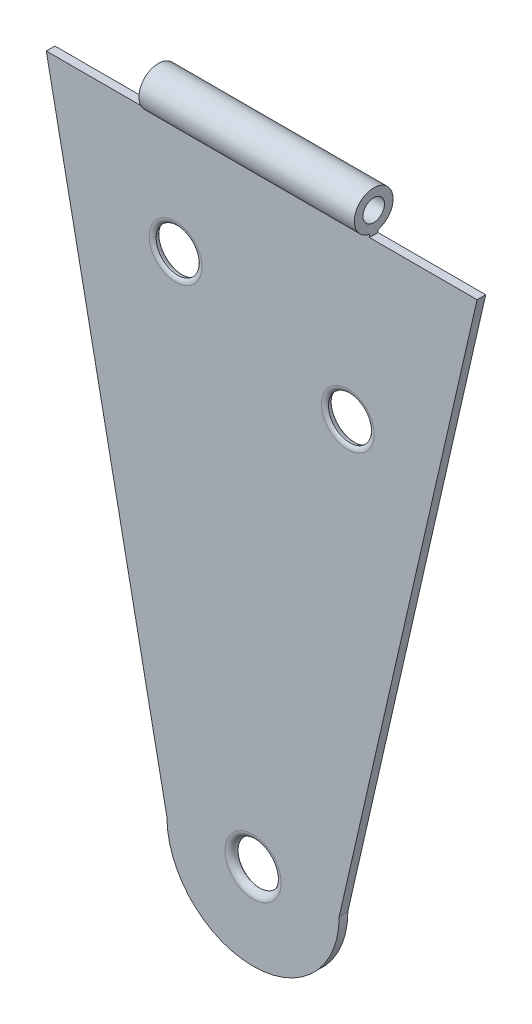
SolidWorks part; units mm, degrees
material "Liga de aço fundido"
ref_plane "Plano frontal" through (0, 0, 0) normal (0, 0, 1) x (1, 0, 0)
ref_plane "Plano superior" through (0, 0, 0) normal (0, 1, 0) x (1, 0, 0)
ref_plane "Plano direito" through (0, 0, 0) normal (1, 0, 0) x (0, 0, -1)
sketch "Esboço1" plane through (0, 0, 0) normal (0, 0, 1) x (1, 0, 0)
  line L0 (-6.1806, 8.1865) -> (-16.1806, 8.1865) construction
  line L2 (-9.8109, 6.3753) -> (-9.8109, 6.1865)
  line L5 (-19.8478, 8.1865) -> (-9.8478, 8.1865)
  line L20 (-9.8109, 6.3753) -> (-9.8109, 6.1865) construction
  line L31 (-19.8478, 8.1865) -> (-17.0478, -5.8135)
  line L33 (-13.0478, -5.8135) -> (-9.8478, 8.1865)
  circle A0 centre (-12.8478, 4.2833) radius 0.5
  circle A5 centre (-16.8478, 5.6526) radius 0.5
  arc A7 (-17.0478, -5.8135) -> (-13.0478, -5.8135) centre (-15.0478, -5.8135) ccw
  circle A8 centre (-15.0478, -5.8135) radius 0.5
  dimension "D3" = 1
  dimension "D1" = 4
  dimension "D2" = 10
  dimension "D4" = 14
  dimension "D5" = 281.31
extrude "Ressalto-extrusão1" add sketch "Esboço1" along normal blind 0.2 contours L2 A0 region at (-14.941, 1.6598, 0)
fillet "Filete1" radius 0.15 3 edges at (-16.3478, 5.6526, 0) (-12.3478, 4.2833, 0) (-14.5478, -5.8135, 0.2)
fillet "Filete2" radius 0.15 3 edges at (-12.3478, 4.2833, 0.2) (-16.3478, 5.6526, 0.2) (-14.5478, -5.8135, 0)
sketch "Esboço6" plane through (0, 8.1865, 0) normal (0, 1, 0) x (1, 0, 0)
  line L4 (-9.8478, 0) -> (-19.8478, 0)
  line L5 (-19.8478, 0) -> (-19.8478, -0.2)
  line L6 (-19.8478, -0.2) -> (-9.8478, -0.2)
  line L7 (-9.8478, -0.2) -> (-9.8478, 0)
  line L8 (-9.8478, 0) -> (-19.8478, 0)
  line L9 (-19.8478, 0) -> (-19.8478, -0.2)
  line L10 (-19.8478, -0.2) -> (-9.8478, -0.2)
  line L11 (-9.8478, -0.2) -> (-9.8478, 0)
  dimension "D1" = 0
extrude "Ressalto-extrusão2" add sketch "Esboço6" along normal blind 0.5
sketch "Esboço7" plane through (-9.8478, 0, 0) normal (1, 0, 0) x (0, 0, -1)
  line L0 (-0.2, 8.1865) -> (0, 8.6865) construction
  line L4 (-0.2, 8.1865) -> (0, 8.1865)
  line L5 (0, 8.1865) -> (0, 8.6865)
  line L6 (0, 8.6865) -> (-0.2, 8.6865)
  line L7 (-0.2, 8.6865) -> (-0.2, 8.1865)
  line L8 (-0.2, 8.1865) -> (0, 8.1865)
  line L9 (0, 8.1865) -> (0, 8.6865)
  line L10 (0, 8.6865) -> (-0.2, 8.6865)
  line L11 (-0.2, 8.6865) -> (-0.2, 8.1865)
  circle A0 centre (-0.1, 8.6865) radius 0.25
  circle A1 centre (-0.1, 8.6865) radius 0.45
  dimension "D2" = 0.5
  dimension "D3" = 0.2
  dimension "D1" = 0
extrude "Ressalto-extrusão3" add sketch "Esboço7" against normal blind 10 contours L9 A1 L11 A0 region at (-9.8478, 9.0284, 0.3727)
sketch "Esboço8" plane through (-9.8478, 0, 0) normal (1, 0, 0) x (0, 0, -1)
  arc A0 (0, 8.4574) -> (-0.2, 8.4574) centre (-0.1, 8.6865) ccw construction
  arc A1 (0, 8.4574) -> (-0.2, 8.4574) centre (-0.1, 8.6865) ccw
  circle A2 centre (-0.1, 8.6865) radius 0.25
  arc M1 (-0.2, 8.4574) -> (0, 8.4574) centre (-0.1, 8.6865) cw
  line M2 (0, 8.4574) -> (0, 8.6865)
  line M3 (0, 8.6865) -> (-0.2, 8.6865)
  line M4 (-0.2, 8.6865) -> (-0.2, 8.4574)
extrude "Corte-extrusão1" cut sketch "Esboço8" against normal blind 10 contours M1 M4 M3 M2 | A2 M4 M2 M3 region at (-9.8478, 8.7266, 0.1) region at (-9.8478, 8.5648, 0.1)
sketch "Esboço9" plane through (0, 0, 0) normal (0, 0, -1) x (-1, 0, 0)
  line L1 (9.8478, 8.1865) -> (12.3478, 8.1865)
  line L2 (9.8478, 8.1865) -> (9.8478, 10.1865)
  line L3 (9.8478, 10.1865) -> (12.3478, 10.1865)
  line L4 (12.3478, 8.1865) -> (12.3478, 10.1865)
  line L5 (19.8478, 8.1865) -> (17.3478, 8.1865)
  line L6 (19.8478, 8.1865) -> (19.8478, 10.1865)
  line L7 (19.8478, 10.1865) -> (17.3478, 10.1865)
  line L8 (17.3478, 8.1865) -> (17.3478, 10.1865)
extrude "Corte-extrusão2" cut sketch "Esboço9" against normal blind 10 and the other way blind 10
